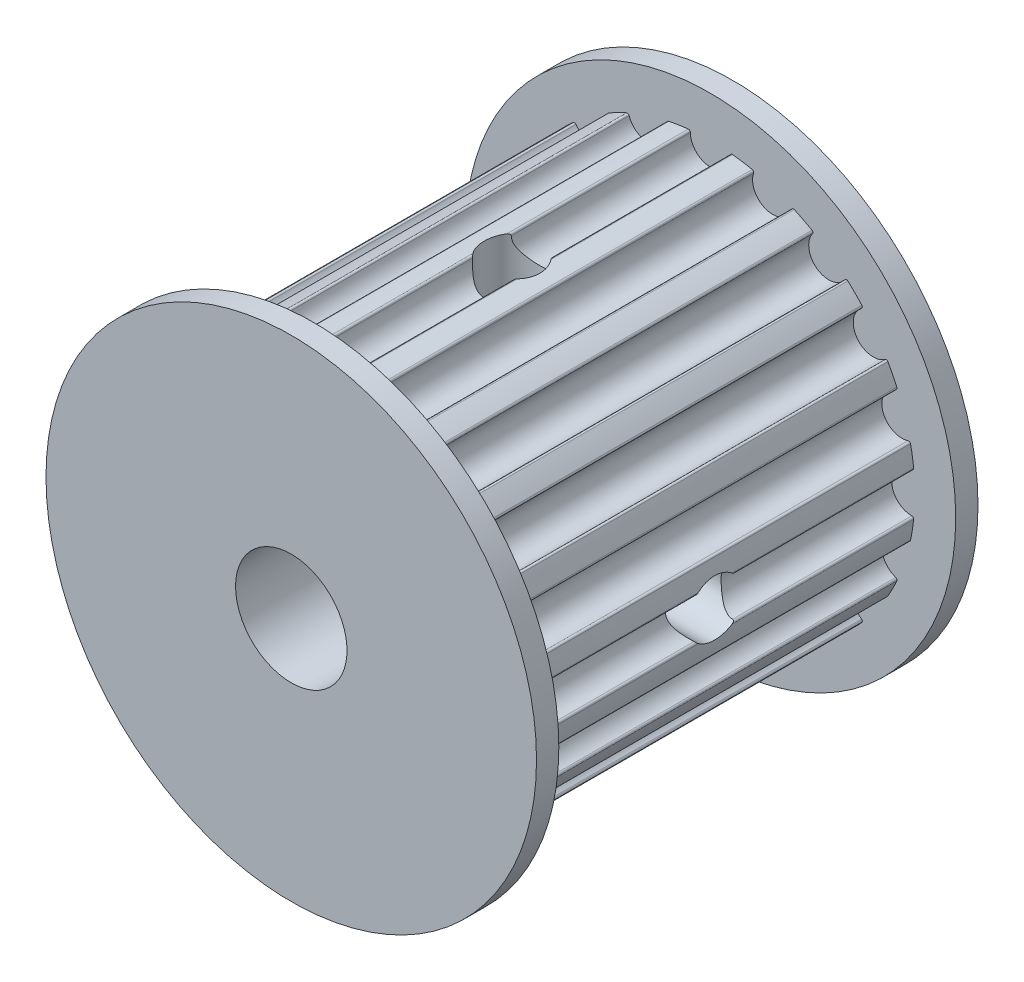
SolidWorks part; units mm, degrees
material "6061-T6 (SS)"
ref_plane "前视基准面" through (0, 0, 0) normal (0, 0, 1) x (1, 0, 0)
ref_plane "上视基准面" through (0, 0, 0) normal (0, 1, 0) x (1, 0, 0)
ref_plane "右视基准面" through (0, 0, 0) normal (1, 0, 0) x (0, 0, -1)
ref_axis "基准轴1" through (0, 0, 55) along (0, 0, -1)
sketch "旋转草图同步带轮01" plane through (0, 0, 0) normal (1, 0, 0) x (0, 0, -1)
  line L0 (0, 0) -> (1, 0) construction
  line L1 (11.3992, 0) -> (11.3992, 9.1676)
  line L2 (11.3992, 9.1676) -> (-6.4008, 9.1676)
  line L3 (-6.4008, 9.1676) -> (-6.4008, 0)
  line L4 (-6.4008, 0) -> (11.3992, 0)
  dimension "GearBeltOutsideDiameter" = 9.1676
  dimension "D1" = 17.8
revolve "同步带轮01" add sketch "旋转草图同步带轮01" angle 360 about L0
sketch "齿草图同步带轮01" plane through (0, 0, 0) normal (0, 0, 1) x (1, 0, 0)
  line L0 (-0.9936, 9.1136) -> (0, 11.7076)
  line L1 (0, 11.7076) -> (0.9936, 9.1136)
  arc A0 (0.9936, 9.1136) -> (0.9, 9.0296) centre (0.9845, 9.0296) ccw
  arc A1 (0.9, 9.0296) -> (-0.9, 9.0296) centre (0, 9.0296) cw
  arc A2 (-0.9, 9.0296) -> (-0.9936, 9.1136) centre (-0.9845, 9.0296) ccw
  dimension "GearBeltToothR1" = 0.169
  dimension "GearBeltToothR2" = 1.8
  dimension "GearBeltToothCapX1" = 0.9936
  dimension "GearBeltToothCapY1" = 2.594
  dimension "GearBeltToothCapX2" = 0.9936
  dimension "GearBeltToothCapY2" = 2.594
extrude "齿拉伸切除同步带轮01" cut sketch "齿草图同步带轮01" against normal blind 11.5 and the other way blind 6.5
pattern_circular "齿形同步带轮01" count 20 over 360 about axis through (0, 0, 55) along (0, 0, -1) of "齿拉伸切除同步带轮01"
sketch "孔旋转草图" plane through (0, 0, 0) normal (1, 0, 0) x (0, 0, -1)
  line L0 (-6.4008, 0) -> (6.4008, 0)
  line L1 (6.4008, 0) -> (6.4008, 127)
  line L2 (6.4008, 127) -> (-6.4008, 127)
  line L3 (-6.4008, 127) -> (-6.4008, 0)
  dimension "TaperSide1" = 127
  dimension "TaperSide2" = 127
sketch "辅助草图同步带轮01" plane through (0, 0, 0) normal (0, 0, 1) x (1, 0, 0)
  circle A0 centre (0, 0) radius 9.5486 construction
  dimension "PitchDiameter" = 19.0972
sketch "草图5" plane through (0, 0, 6.4008) normal (0, 0, 1) x (1, 0, 0)
  circle A0 centre (0, 0) radius 11
  dimension "D1" = 22
extrude "凸台-拉伸1" add sketch "草图5" along normal blind 1
sketch "草图6" plane through (0, 0, -11.3992) normal (0, 0, -1) x (-1, 0, 0)
  circle A1 centre (0, 0) radius 11
  circle A2 centre (0, 0) radius 11
  dimension "D1" = 0
extrude "凸台-拉伸2" add sketch "草图6" along normal blind 1
sketch "草图7" plane through (0, 0, -12.3992) normal (0, 0, -1) x (-1, 0, 0)
  circle A0 centre (0, 0) radius 2.5
  dimension "D1" = 5
extrude "切除-拉伸2" cut sketch "草图7" against normal through all
ref_plane "基准面1" through (0, 11, 0) normal (0, 1, 0) x (1, 0, 0)
sketch "草图9" plane through (0, 11, 0) normal (0, 1, 0) x (1, 0, 0)
  line L0 (0, -7.4008) -> (0, 12.3992) construction
  line L1 (-11, -7.4008) -> (11, -7.4008) construction
  line L2 (2.5, 12.3992) -> (-2.5, 12.3992) construction
  circle A0 centre (0, 2.4992) radius 2
  dimension "D1" = 4
hole_wizard "M3 螺纹孔1" positions "3D草图2" profile "草图11" tap size "M3" standard "GB"
sketch3d "3D草图2"
  circle A0 centre (0, 11, -2.4992) radius 2 construction
  point P3 (0, 9.1676, -2.4992)
  point P11 (0, 13, -2.4992)
sketch "草图11" plane through (0, 9.1676, -2.4992) normal (1, 0, 0) x (0, 0, 1)
  line L0 (0, 0) -> (0, 8.2511)
  line L1 (0, 8.2511) -> (1.25, 7.5)
  line L2 (1.25, 7.5) -> (1.25, 0)
  line L5 (1.25, 0) -> (0, 0)
  line L10 (0, 8.2511) -> (-1.25, 7.5) construction
  line L11 (0, -6.35) -> (0, 107.95) construction
  dimension "螺纹孔钻头直径" = 2.5
  dimension "螺纹孔钻头深度" = 7.5
  dimension "导头角度" = 118
cosmetic thread "孔螺蚊线1" parameters "D1"=6, "D2"=3
ref_plane "基准面2" through (11, 0, 0) normal (1, 0, 0) x (0, 0, -1)
sketch "草图12" plane through (11, 0, 0) normal (1, 0, 0) x (0, 0, -1)
  line L0 (-7.4008, 0) -> (12.3992, 0) construction
  line L1 (-7.4008, 11) -> (-7.4008, -11) construction
  line L2 (12.3992, -11) -> (12.3992, 11) construction
  circle A0 centre (2.4992, 0) radius 2 construction
  dimension "D1" = 4
hole_wizard "M3 螺纹孔2" positions "3D草图3" profile "草图13" tap size "M3" standard "GB"
sketch3d "3D草图3"
  circle A1 centre (11, 0, -2.4992) radius 2 construction
  point P10 (9.1676, 0, -2.4992)
  point P18 (13, 0, -2.4992)
sketch "草图13" plane through (9.1676, 0, -2.4992) normal (0, 1, 0) x (0, 0, -1)
  line L0 (0, 0) -> (0, 8.2511)
  line L1 (0, 8.2511) -> (1.25, 7.5)
  line L2 (1.25, 7.5) -> (1.25, 0)
  line L5 (1.25, 0) -> (0, 0)
  line L10 (0, 8.2511) -> (-1.25, 7.5) construction
  line L11 (0, -6.35) -> (0, 107.95) construction
  dimension "螺纹孔钻头直径" = 2.5
  dimension "螺纹孔钻头深度" = 7.5
  dimension "导头角度" = 118
cosmetic thread "孔螺蚊线5" parameters "D1"=6, "D2"=3
